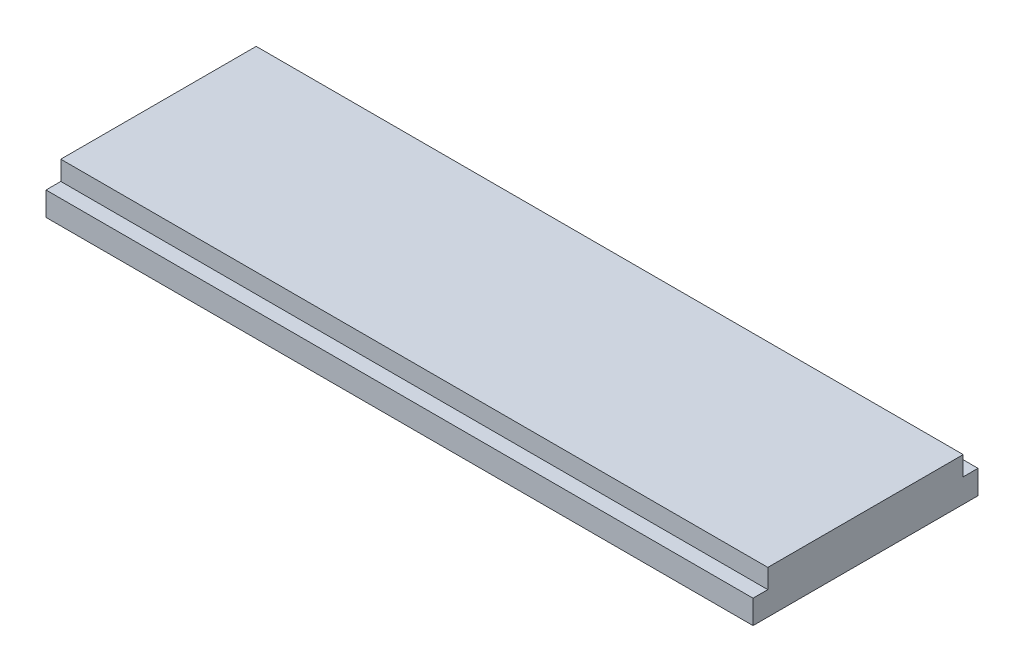
SolidWorks part; units mm, degrees
ref_plane "Front Plane" through (0, 0, 0) normal (0, 0, 1) x (1, 0, 0)
ref_plane "Top Plane" through (0, 0, 0) normal (0, 1, 0) x (1, 0, 0)
ref_plane "Right Plane" through (0, 0, 0) normal (1, 0, 0) x (0, 0, -1)
sketch "Sketch1" plane through (0, 0, 0) normal (0, 1, 0) x (1, 0, 0)
  line L1 (0, 0) -> (1100, 0)
  line L2 (0, 0) -> (0, 350)
  line L3 (0, 350) -> (1100, 350)
  line L4 (1100, 0) -> (1100, 350)
  dimension "D1" = 350
  dimension "D2" = 1100
extrude "Boss-Extrude1" add sketch "Sketch1" along normal blind 67
sketch "Sketch2" plane through (0, 67, 0) normal (0, 1, 0) x (1, 0, 0)
  line L0 (1100, 0) -> (1100, 350) construction
  line L1 (0, 0) -> (1100, 0)
  line L2 (0, 0) -> (0, 23)
  line L3 (0, 23) -> (1100, 23)
  line L4 (1100, 0) -> (1100, 23)
  line L5 (0, 175) -> (1509.6888, 175) construction
  line L6 (0, 350) -> (0, 0) construction
  line L7 (0, 327) -> (1100, 327)
  line L8 (1100, 350) -> (1100, 327)
  line L9 (0, 350) -> (1100, 350)
  line L10 (0, 350) -> (0, 327)
  dimension "D1" = 23
extrude "Cut-Extrude1" cut sketch "Sketch2" against normal blind 30
